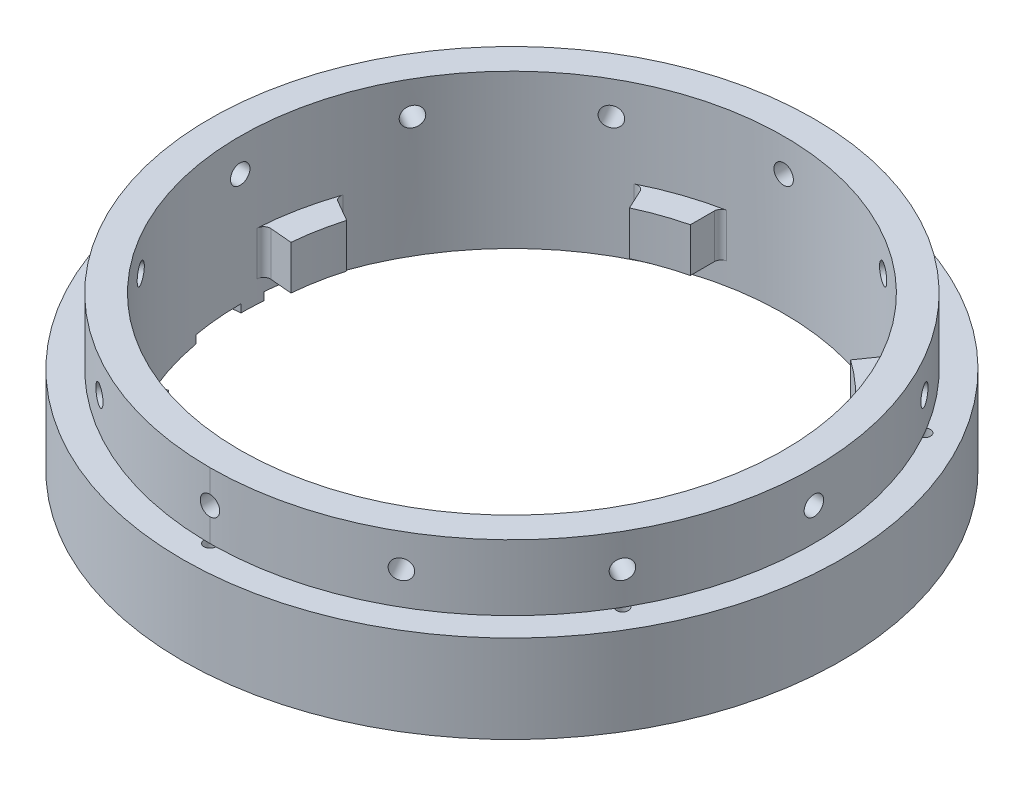
SolidWorks part; units mm, degrees
ref_plane "Front Plane" through (0, 0, 0) normal (0, 0, 1) x (1, 0, 0)
ref_plane "Top Plane" through (0, 0, 0) normal (0, 1, 0) x (1, 0, 0)
ref_plane "Right Plane" through (0, 0, 0) normal (1, 0, 0) x (0, 0, -1)
sketch "Sketch1" plane through (0, 0, 0) normal (0, 1, 0) x (1, 0, 0)
  circle A0 centre (0, 0) radius 69.85
  circle A1 centre (0, 0) radius 76.2
  circle A2 centre (0, 0) radius 56.1975
  circle A4 centre (0, 0) radius 62.865
  dimension "D1" = 152.4
  dimension "D3" = 112.395
  dimension "D2" = 6.35
  dimension "D4" = 13.335
extrude "Boss-Extrude1" add sketch "Sketch1" along normal blind 20.2692 contours A0 A2 | A0 A4 region at (-67.8743, 0, 0) region at (-61.0869, 0, 0)
extrude "Boss-Extrude2" add sketch "Sketch1<4>" along normal blind 5.08 and the other way blind 15.24 contours A1 A0 | A0 A4 region at (-67.8743, 0, 0) region at (-74.0447, 0, 0)
sketch "Sketch1<4>" plane through (0, 0, 0) normal (0, 1, 0) x (1, 0, 0) same geometry as "Sketch1"
sketch "Sketch3" plane through (0, -15.24, 0) normal (0, -1, 0) x (1, 0, 0)
  line L0 (0, 0) -> (-65.7887, 5.7558) construction
  line L1 (0, 0) -> (0, 69.85) construction
  line L2 (0, 0) -> (48.9804, 58.3726)
  line L3 (0, 0) -> (13.232, 75.0424)
  line L4 (-13.335, -54.5925) -> (-13.335, -60.117)
  line L5 (13.335, -54.5925) -> (13.335, -60.117)
  line L6 (-13.335, -60.117) -> (13.335, -60.117)
  line L7 (-13.335, -60.117) -> (-13.335, -61.4344)
  line L8 (-23.7501, -50.9322) -> (-26.5679, -56.975)
  line L9 (0, 0) -> (-23.7501, -50.9322) construction
  line L10 (-65.2934, 11.4174) -> (-61.874, 11.1182)
  line L11 (-66.284, 0.0941) -> (-62.8647, -0.205)
  line L12 (-66.0236, -5.8708) -> (-62.6433, -5.2748)
  line L13 (-64.0498, -17.0646) -> (-60.6695, -16.4686)
  line L14 (-65.0367, -11.4677) -> (0, 0) construction
  line L15 (27.9275, 60.1135) -> (26.7536, 56.8881)
  line L16 (17.2465, 64.0011) -> (16.0725, 60.7757)
  line L17 (38.0961, -54.2427) -> (35.8898, -51.6133)
  line L18 (46.8033, -46.9365) -> (44.597, -44.3071)
  circle A0 centre (-65.7887, 5.7558) radius 5.6833
  circle A1 centre (0, 69.85) radius 1.3589
  circle A2 centre (0, 0) radius 76.2 construction
  circle A5 centre (0, 0) radius 56.1975 construction
  arc A7 (-26.5679, -56.975) -> (-13.335, -61.4344) centre (0, 0) ccw
  arc A9 (-23.7501, -50.9322) -> (-13.335, -54.5925) centre (0, 0) ccw
  circle A10 centre (-65.7887, 5.7558) radius 2.5083
  circle A11 centre (-65.0367, -11.4677) radius 5.6832
  circle A12 centre (0, 0) radius 62.865 construction
  circle A13 centre (-65.0367, -11.4677) radius 2.5082
  circle A14 centre (0, 0) radius 62.865 construction
  circle A15 centre (22.587, 62.0573) radius 5.6832
  circle A16 centre (22.587, 62.0573) radius 2.5082
  circle A17 centre (42.4497, -50.5896) radius 5.6832
  circle A18 centre (42.4497, -50.5896) radius 2.5082
  arc A19 (-62.6433, -5.2748) -> (-60.6695, -16.4686) centre (0, 0) ccw
  point P0 (0, -60.117)
  point P38 (0, 0)
  point P56 (0, 0)
  circle M49 centre (0, 0) radius 62.865
  dimension "D4" = 11.3665
  dimension "D5" = 2.7178
  dimension "D11" = 5.0165
  dimension "D1" = 66.04
  dimension "D2" = 85
  dimension "D3" = 69.85
  dimension "D6" = 30
  dimension "D7" = 10
  dimension "D9" = 26.67
  dimension "D8" = 5.5245
  dimension "D10" = 25
  dimension "D13" = 15
  dimension "D12" = 2
  dimension "D14" = 3
extrude "Cut-Extrude1" cut sketch "Sketch3" against normal blind 1.8415 contours A11 A13 M49 | A11 L13 M49 | A13 | A11 L12 M49 | A0 A10 M49 | A10 | A0 L11 M49 | A0 L10 M49 region at (-62.774, -15.24, 10.8743) region at (-63.6243, -15.24, 10.8507) region at (-63.7086, -15.24, 0.1915) region at (-63.4495, -15.24, -5.7433) region at (-64.265, -15.24, -5.9885) region at (-61.5874, -15.24, -16.304) region at (-65.7887, -15.24, 5.7558) region at (-65.0367, -15.24, -11.4677)
extrude "Cut-Extrude2" cut sketch "Sketch3<3>" against normal up to surface (20.32 mm away) contours A1 region at (0, -15.24, 69.85) up to face at (0, 5.08, 69.85)
sketch "Sketch3<3>" plane through (0, -15.24, 0) normal (0, -1, 0) x (1, 0, 0) same geometry as "Sketch3"
sketch "Sketch6" plane through (0, -13.3985, 0) normal (0, -1, 0) x (1, 0, 0)
  line L0 (-65.0367, -11.4677) -> (0, 0) construction
  line L1 (0, 0) -> (-65.7887, 5.7558) construction
  arc A0 (-65.2934, 11.4174) -> (-66.284, 0.0941) centre (-65.7887, 5.7558) ccw construction
  arc A1 (-65.2934, 11.4174) -> (-66.284, 0.0941) centre (-65.7887, 5.7558) ccw
  circle A2 centre (-65.7887, 5.7558) radius 2.5083
  circle A3 centre (-65.0367, -11.4677) radius 2.5082
  point P9 (0, 0)
  dimension "D1" = 5.0165
  dimension "D3" = 15
extrude "Cut-Extrude4" cut sketch "Sketch6" against normal up to surface (18.4785 mm away) contours A2 | A3 region at (-65.7887, -13.3985, 5.7558) up to face at (0, 5.08, 0.6795)
pattern_circular "CirPattern1" count 3 over 360 about axis through (0, -15.24, 0) along (0, 1, 0) of "Cut-Extrude1", "Cut-Extrude4"
pattern_circular "CirPattern2" count 6 over 360 about axis through (0, -15.24, 0) along (0, 1, 0) of "Cut-Extrude2"
ref_plane "Plane1" through (0, 0, 76.2) normal (0, 0, 1) x (1, 0, 0)
sketch "Sketch5" plane through (0, 0, 76.2) normal (0, 0, 1) x (1, 0, 0)
  line L0 (0, -15.24) -> (0, 12.6746) construction
  line L1 (-1.3589, -15.24) -> (1.3589, -15.24) construction
  circle A0 centre (0, 12.6746) radius 2.2479
  dimension "D2" = 4.4958
  dimension "D1" = 27.9146
extrude "Cut-Extrude3" cut sketch "Sketch5" against normal up to surface (20.0475 mm away) up to face at (0, 20.2692, 56.1975)
extrude "Boss-Extrude3" add sketch "Sketch3<11>" along normal blind 10.16 from surface contours L4 A9 L8 A7 L7 starting at face at (0, 0, 56.1975)
sketch "Sketch3<11>" plane through (0, -15.24, 0) normal (0, -1, 0) x (1, 0, 0) same geometry as "Sketch3"
pattern_circular "CirPattern3" count 6 over 360 about axis through (0, 20.2692, 0) along (0, 1, 0) of "Boss-Extrude3"
fillet "Fillet1" radius 1.5875 12 edges at (-62.6258, -5.08, -5.479) (-59.8713, -5.08, -19.1688) (-26.5679, -5.08, -56.975) (-13.335, -5.08, -61.4344) (36.0579, -5.08, -51.496) (46.5363, -5.08, -42.2657) (62.6258, -5.08, 5.479) (59.8713, -5.08, 19.1688) (26.5679, -5.08, 56.975) (13.335, -5.08, 61.4344) (-36.0579, -5.08, 51.496) (-46.5363, -5.08, 42.2657)
pattern_circular "CirPattern4" count 12 over 360 about axis through (0, 20.2692, 0) along (0, 1, 0) of "Cut-Extrude3"
sketch "Sketch8" plane through (0, 20.2692, 0) normal (0, 1, 0) x (1, 0, 0)
  arc A0 (-34.7117, -52.4129) -> (12.0518, -61.699) centre (0, 0) ccw construction
  arc A1 (-34.7117, -52.4129) -> (12.0518, -61.699) centre (0, 0) ccw
  circle A2 centre (0, 0) radius 62.865
  circle M2 centre (0, 0) radius 56.1975
extrude "Cut-Extrude5" cut sketch "Sketch8" against normal up to surface (20.2692 mm away) contours A1 A2 M2 region at (-28.9064, 20.2692, -53.8148) up to face at (42.8898, 0, 37.3465)
sketch "Sketch9" plane through (0, 0, 0) normal (0, 0, 1) x (1, 0, 0)
  line L0 (0, 5.08) -> (0, 20.2692)
  line L1 (76.2, 5.08) -> (-76.2, 5.08) construction
  line L2 (69.85, 20.2692) -> (-69.85, 20.2692) construction
split line "Split Line2"
equation "\"Middle Coupler Inner Daimeter\"= 3.875in"
equation "\"Middle Coupler  Wall Thickness\" = 0.25in"
equation "\"Middle Coupler Bottom Thickness\"= 0.2in"
equation "\"Bearing Rail Offset\"= 0.45in"
equation "\"3-56 UNF Tap\"= 0.089in"
equation "\"3-48 Tap\"= 0.079in"
equation "\"3-56 UNF Clearance\"= 0.104in"
equation "\"3-48 Clearance\" = 0.104in"
equation "\"Ball Bearing Distance\"= 0.03in"
equation "\"TCA Outer Diameter\" = 6in"
equation "\"Interstage Aeroframe Wall Thickness\" = 0.072in"
equation "\"Compression Spring OD\"= 0.42in"
equation "\"10-24 Tap\"= 0.157in"
equation "\"10-24 Clearance\"= 0.196in"
equation "\"Lower Stage Fuselage Wall Thickness\" = 0.25in"
equation "\"6-32 Tap\" = 0.107in"
equation "\"6-32 Clearance\" = 0.144"
equation "\"1/4-20 Tap\" = 0.201in"
equation "\"12-24 Tap\" = 0.177in"
equation "\"D1@Sketch1\"=\"TCA Outer Diameter\""
equation "\"D5@Sketch3\"=\"6-32 Tap\""
equation "\"D1@Sketch5\"=\"D2@Boss-Extrude2\"+(\"D1@Boss-Extrude2\"+\"D1@Boss-Extrude1\")/2"
equation "\"D2@Sketch5\"=\"12-24 Tap\""
equation "\"D8@Sketch3\"=3/16+0.03"
equation "\"D3@Sketch1\"=\"Middle Coupler Inner Daimeter\" + 0.55"
equation "\"D4@Sketch3\"=7/16 + 0.01"
equation "\"D1@Boss-Extrude1\"=0.15 + \"12-24 Major Diameter\"*3"
equation "\"12-24 Major Diameter\"= 0.216in"
equation "\"D1@Cut-Extrude1\"=1/16 + 0.01"
equation "\"D11@Sketch3\"=3/16 + 0.01"
equation "\"D1@Sketch6\"=3/16 + 0.01"
